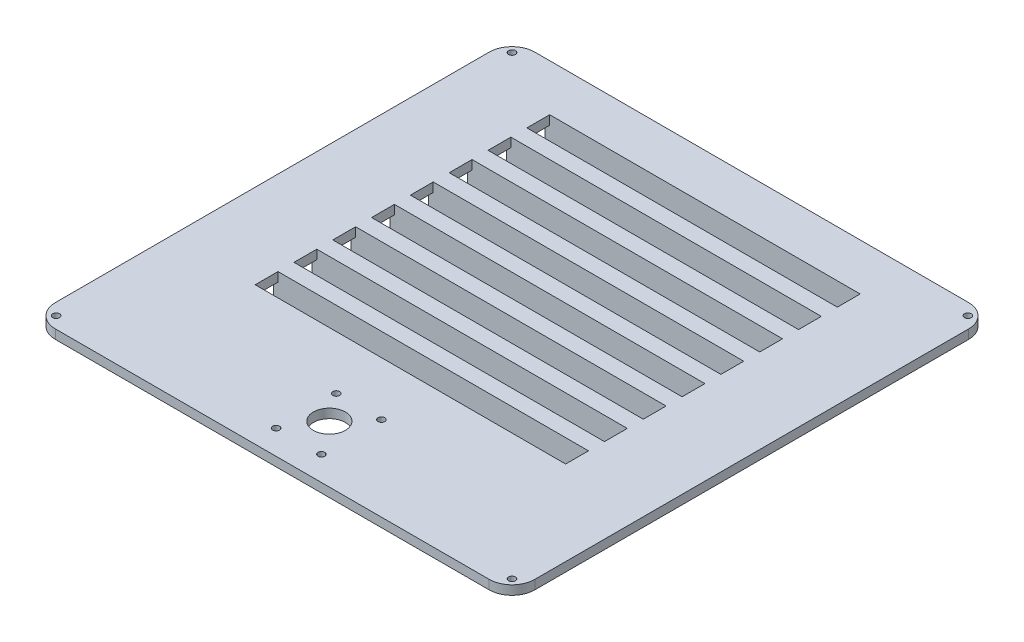
SolidWorks part; units mm, degrees
ref_plane "Front Plane" through (0, 0, 0) normal (0, 0, 1) x (1, 0, 0)
ref_plane "Top Plane" through (0, 0, 0) normal (0, 1, 0) x (1, 0, 0)
ref_plane "Right Plane" through (0, 0, 0) normal (1, 0, 0) x (0, 0, -1)
sketch "Sketch1" plane through (0, 0, 0) normal (0, 1, 0) x (1, 0, 0)
  line L0 (-101, -101) -> (-101, 101)
  line L5 (-105, -105) -> (105, -105)
  line L6 (-105, -105) -> (-105, 105)
  line L7 (-105, 105) -> (105, 105)
  line L8 (105, -105) -> (105, 105)
  line L9 (-101, 101) -> (101, 101)
  line L10 (101, -101) -> (101, 101)
  line L11 (-101, -101) -> (101, -101)
  line L12 (-101, 101) -> (-99.8333, 99.8333) construction
  line L13 (-55, 0) -> (55, 0) construction
  line L14 (-101, -101) -> (-99.8333, -99.8333) construction
  line L15 (0, -55) -> (0, 55) construction
  line L16 (101, -101) -> (99.8333, -99.8333) construction
  line L17 (101, 101) -> (99.8333, 99.8333) construction
  circle A1 centre (-99.8333, 99.8333) radius 1.5
  circle A2 centre (-99.8333, -99.8333) radius 1.5
  circle A3 centre (99.8333, -99.8333) radius 1.5
  circle A4 centre (99.8333, 99.8333) radius 1.5
  point P0 (0, 0)
  point P6 (-105, 0)
  point P7 (0, 105)
  dimension "D3" = 4
  dimension "D4" = 3
  dimension "D1" = 210
  dimension "D2" = 210
  dimension "D5" = 1.65
  dimension "D6" = 45
extrude "MainExtrude" add sketch "Sketch1" along normal blind 4 contours L6 L5 L8 L7
extrude "ScrewHoles" cut sketch "Sketch1<6>" along normal up to surface (4 mm away) contours A1 | A2 | A3 | A4 up to face at (0, 4, 0)
sketch "Sketch1<6>" plane through (0, 0, 0) normal (0, 1, 0) x (1, 0, 0) same geometry as "Sketch1"
fillet "RoundedCorners" radius 10 4 edges at (-105, 2, -105) (-105, 2, 105) (105, 2, -105) (105, 2, 105)
sketch "Sketch3" plane through (0, 0, 0) normal (0, 1, 0) x (1, 0, 0)
  line L145 (-68, 96.5) -> (68, 96.5) construction
  line L146 (-68, 96.5) -> (-68, -56.5) construction
  line L147 (-68, -56.5) -> (68, -56.5) construction
  line L148 (68, 96.5) -> (68, -56.5) construction
  line L149 (-68, 96.5) -> (68, -56.5) construction
  line L151 (68, 96.5) -> (-68, -56.5) construction
  line L152 (-68, 79.5) -> (68, 79.5) construction
  line L154 (-68, 62.5) -> (68, 62.5) construction
  line L155 (-68, 45.5) -> (68, 45.5) construction
  line L157 (-68, 28.5) -> (68, 28.5) construction
  line L158 (-68, 11.5) -> (68, 11.5) construction
  line L159 (-68, -5.5) -> (68, -5.5) construction
  line L160 (-68, -22.5) -> (68, -22.5) construction
  line L161 (-68, -39.5) -> (68, -39.5) construction
  line L162 (-68, 74.5) -> (68, 74.5)
  line L163 (-68, 57.5) -> (68, 57.5)
  line L164 (-68, 40.5) -> (68, 40.5)
  line L165 (-68, 23.5) -> (68, 23.5)
  line L166 (-68, 6.5) -> (68, 6.5)
  line L167 (-68, -10.5) -> (68, -10.5)
  line L168 (-68, -27.5) -> (68, -27.5)
  line L169 (-68, -44.5) -> (68, -44.5)
  line L170 (-68, 84.5) -> (68, 84.5)
  line L171 (-68, 67.5) -> (68, 67.5)
  line L172 (-68, 50.5) -> (68, 50.5)
  line L173 (-68, 33.5) -> (68, 33.5)
  line L174 (-68, 16.5) -> (68, 16.5)
  line L175 (-68, -0.5) -> (68, -0.5)
  line L176 (-68, -17.5) -> (68, -17.5)
  line L177 (-68, -34.5) -> (68, -34.5)
  line L178 (-68, 74.5) -> (-68, 84.5)
  line L179 (68, 74.5) -> (68, 84.5)
  line L180 (-68, 57.5) -> (-68, 67.5)
  line L181 (68, 57.5) -> (68, 67.5)
  line L182 (-68, 40.5) -> (-68, 50.5)
  line L183 (68, 40.5) -> (68, 50.5)
  line L184 (-68, 23.5) -> (-68, 33.5)
  line L185 (68, 23.5) -> (68, 33.5)
  line L186 (-68, 6.5) -> (-68, 16.5)
  line L187 (68, 6.5) -> (68, 16.5)
  line L188 (-68, -10.5) -> (-68, -0.5)
  line L189 (68, -10.5) -> (68, -0.5)
  line L190 (-68, -27.5) -> (-68, -17.5)
  line L191 (68, -27.5) -> (68, -17.5)
  line L192 (-68, -44.5) -> (-68, -34.5)
  line L193 (68, -44.5) -> (68, -34.5)
  line L200 (-9, -68) -> (-9, -94.3) construction
  line L201 (-95, -105) -> (95, -105) construction
  line L207 (-97.2358, 20) -> (95.5763, 20) construction
  line L208 (-9, -68) -> (10.8, -68) construction
  circle A0 centre (0, -80) radius 7
  circle A1 centre (-9, -68) radius 1.5
  circle A2 centre (-9, -94.3) radius 1.5
  circle A3 centre (10.8, -94.3) radius 1.5
  circle A4 centre (10.8, -68) radius 1.5
  point P57 (0, 0)
  point P58 (0, 0)
  point P59 (0, 0)
  point P62 (-1.9194, -80.5562)
  point P70 (0, 20)
  dimension "D18" = 14
  dimension "D19" = 25
  dimension "D21" = 35.5
  dimension "D25" = 3
  dimension "D26" = 3
  dimension "D27" = 19.8
  dimension "D15" = 9
  dimension "D16" = 12
  dimension "D1" = 136
  dimension "D2" = 153
  dimension "D3" = 17
  dimension "D4" = 17
  dimension "D5" = 17
  dimension "D6" = 17
  dimension "D7" = 17
  dimension "D8" = 17
  dimension "D9" = 17
  dimension "D11" = 17
  dimension "D13" = 5
  dimension "D14" = 129
  dimension "D10" = 17
  dimension "D12" = 5
  dimension "D17" = 10.8
  dimension "D20" = 20
  dimension "D22" = 14.3
  dimension "D28" = 26.3
extrude "Trench" cut sketch "Sketch3" along normal blind 10
sketch "Sketch4" plane through (0, 0, 0) normal (0, 1, 0) x (1, 0, 0)
  line L0 (68, -34.5) -> (68, -44.5) construction
  line L1 (68, -44.5) -> (-68, -44.5) construction
  line L2 (-68, -44.5) -> (-68, -34.5) construction
  line L3 (-68, -34.5) -> (68, -34.5) construction
  line L4 (68, -17.5) -> (68, -27.5) construction
  line L5 (68, -27.5) -> (-68, -27.5) construction
  line L6 (-68, -27.5) -> (-68, -17.5) construction
  line L7 (-68, -17.5) -> (68, -17.5) construction
  line L8 (68, -0.5) -> (68, -10.5) construction
  line L9 (68, -10.5) -> (-68, -10.5) construction
  line L10 (-68, -10.5) -> (-68, -0.5) construction
  line L11 (-68, -0.5) -> (68, -0.5) construction
  line L12 (68, 16.5) -> (68, 6.5) construction
  line L13 (68, 6.5) -> (-68, 6.5) construction
  line L14 (-68, 6.5) -> (-68, 16.5) construction
  line L15 (-68, 16.5) -> (68, 16.5) construction
  line L16 (68, 33.5) -> (68, 23.5) construction
  line L17 (68, 23.5) -> (-68, 23.5) construction
  line L18 (-68, 23.5) -> (-68, 33.5) construction
  line L19 (-68, 33.5) -> (68, 33.5) construction
  line L20 (68, 50.5) -> (68, 40.5) construction
  line L21 (68, 40.5) -> (-68, 40.5) construction
  line L22 (-68, 40.5) -> (-68, 50.5) construction
  line L23 (-68, 50.5) -> (68, 50.5) construction
  line L24 (68, 67.5) -> (68, 57.5) construction
  line L25 (68, 57.5) -> (-68, 57.5) construction
  line L26 (-68, 57.5) -> (-68, 67.5) construction
  line L27 (-68, 67.5) -> (68, 67.5) construction
  line L28 (68, 84.5) -> (68, 74.5) construction
  line L29 (68, 74.5) -> (-68, 74.5) construction
  line L30 (-68, 74.5) -> (-68, 84.5) construction
  line L31 (-68, 84.5) -> (68, 84.5) construction
  line L32 (68, -34.5) -> (68, -44.5)
  line L33 (68, -44.5) -> (-68, -44.5)
  line L34 (-68, -44.5) -> (-68, -34.5)
  line L35 (-68, -34.5) -> (68, -34.5)
  line L36 (68, -17.5) -> (68, -27.5)
  line L37 (68, -27.5) -> (-68, -27.5)
  line L38 (-68, -27.5) -> (-68, -17.5)
  line L39 (-68, -17.5) -> (68, -17.5)
  line L40 (68, -0.5) -> (68, -10.5)
  line L41 (68, -10.5) -> (-68, -10.5)
  line L42 (-68, -10.5) -> (-68, -0.5)
  line L43 (-68, -0.5) -> (68, -0.5)
  line L44 (68, 16.5) -> (68, 6.5)
  line L45 (68, 6.5) -> (-68, 6.5)
  line L46 (-68, 6.5) -> (-68, 16.5)
  line L47 (-68, 16.5) -> (68, 16.5)
  line L48 (68, 33.5) -> (68, 23.5)
  line L49 (68, 23.5) -> (-68, 23.5)
  line L50 (-68, 23.5) -> (-68, 33.5)
  line L51 (-68, 33.5) -> (68, 33.5)
  line L52 (68, 50.5) -> (68, 40.5)
  line L53 (68, 40.5) -> (-68, 40.5)
  line L54 (-68, 40.5) -> (-68, 50.5)
  line L55 (-68, 50.5) -> (68, 50.5)
  line L56 (68, 67.5) -> (68, 57.5)
  line L57 (68, 57.5) -> (-68, 57.5)
  line L58 (-68, 57.5) -> (-68, 67.5)
  line L59 (-68, 67.5) -> (68, 67.5)
  line L60 (68, 84.5) -> (68, 74.5)
  line L61 (68, 74.5) -> (-68, 74.5)
  line L62 (-68, 74.5) -> (-68, 84.5)
  line L63 (-68, 84.5) -> (68, 84.5)
  line L64 (70, 86.5) -> (70, 72.5)
  line L65 (70, 72.5) -> (-70, 72.5)
  line L66 (-70, 72.5) -> (-70, 86.5)
  line L67 (-70, 86.5) -> (70, 86.5)
  line L68 (70, 69.5) -> (70, 55.5)
  line L69 (70, 55.5) -> (-70, 55.5)
  line L70 (-70, 55.5) -> (-70, 69.5)
  line L71 (-70, 69.5) -> (70, 69.5)
  line L72 (70, 52.5) -> (70, 38.5)
  line L73 (70, 38.5) -> (-70, 38.5)
  line L74 (-70, 38.5) -> (-70, 52.5)
  line L75 (-70, 52.5) -> (70, 52.5)
  line L76 (70, 35.5) -> (70, 21.5)
  line L77 (70, 21.5) -> (-70, 21.5)
  line L78 (-70, 21.5) -> (-70, 35.5)
  line L79 (-70, 35.5) -> (70, 35.5)
  line L80 (70, 18.5) -> (70, 4.5)
  line L81 (70, 4.5) -> (-70, 4.5)
  line L82 (-70, 4.5) -> (-70, 18.5)
  line L83 (-70, 18.5) -> (70, 18.5)
  line L84 (70, 1.5) -> (70, -12.5)
  line L85 (70, -12.5) -> (-70, -12.5)
  line L86 (-70, -12.5) -> (-70, 1.5)
  line L87 (-70, 1.5) -> (70, 1.5)
  line L88 (70, -15.5) -> (70, -29.5)
  line L89 (70, -29.5) -> (-70, -29.5)
  line L90 (-70, -29.5) -> (-70, -15.5)
  line L91 (-70, -15.5) -> (70, -15.5)
  line L92 (70, -32.5) -> (70, -46.5)
  line L93 (70, -46.5) -> (-70, -46.5)
  line L94 (-70, -46.5) -> (-70, -32.5)
  line L95 (-70, -32.5) -> (70, -32.5)
  dimension "D1" = 2
extrude "Trench Walls" add sketch "Sketch4" against normal blind 4
sketch "Sketch5" plane through (0, -4, 0) normal (0, -1, 0) x (1, 0, 0)
  line L0 (-70, -86.5) -> (70, -86.5) construction
  line L1 (70, -86.5) -> (70, -72.5) construction
  line L2 (70, -72.5) -> (-70, -72.5) construction
  line L3 (-70, -72.5) -> (-70, -86.5) construction
  line L4 (-70, -69.5) -> (70, -69.5) construction
  line L5 (70, -69.5) -> (70, -55.5) construction
  line L6 (70, -55.5) -> (-70, -55.5) construction
  line L7 (-70, -55.5) -> (-70, -69.5) construction
  line L8 (-70, -52.5) -> (70, -52.5) construction
  line L9 (70, -52.5) -> (70, -38.5) construction
  line L10 (70, -38.5) -> (-70, -38.5) construction
  line L11 (-70, -38.5) -> (-70, -52.5) construction
  line L12 (-70, -35.5) -> (70, -35.5) construction
  line L13 (70, -35.5) -> (70, -21.5) construction
  line L14 (70, -21.5) -> (-70, -21.5) construction
  line L15 (-70, -21.5) -> (-70, -35.5) construction
  line L16 (-70, -18.5) -> (70, -18.5) construction
  line L17 (70, -18.5) -> (70, -4.5) construction
  line L18 (70, -4.5) -> (-70, -4.5) construction
  line L19 (-70, -4.5) -> (-70, -18.5) construction
  line L20 (-70, -1.5) -> (70, -1.5) construction
  line L21 (70, -1.5) -> (70, 12.5) construction
  line L22 (70, 12.5) -> (-70, 12.5) construction
  line L23 (-70, 12.5) -> (-70, -1.5) construction
  line L24 (-70, 15.5) -> (70, 15.5) construction
  line L25 (70, 15.5) -> (70, 29.5) construction
  line L26 (70, 29.5) -> (-70, 29.5) construction
  line L27 (-70, 29.5) -> (-70, 15.5) construction
  line L28 (-70, 32.5) -> (70, 32.5) construction
  line L29 (70, 32.5) -> (70, 46.5) construction
  line L30 (70, 46.5) -> (-70, 46.5) construction
  line L31 (-70, 46.5) -> (-70, 32.5) construction
  line L32 (-70, -86.5) -> (70, -86.5)
  line L33 (70, -86.5) -> (70, -72.5)
  line L34 (70, -72.5) -> (-70, -72.5)
  line L35 (-70, -72.5) -> (-70, -86.5)
  line L36 (-70, -69.5) -> (70, -69.5)
  line L37 (70, -69.5) -> (70, -55.5)
  line L38 (70, -55.5) -> (-70, -55.5)
  line L39 (-70, -55.5) -> (-70, -69.5)
  line L40 (-70, -52.5) -> (70, -52.5)
  line L41 (70, -52.5) -> (70, -38.5)
  line L42 (70, -38.5) -> (-70, -38.5)
  line L43 (-70, -38.5) -> (-70, -52.5)
  line L44 (-70, -35.5) -> (70, -35.5)
  line L45 (70, -35.5) -> (70, -21.5)
  line L46 (70, -21.5) -> (-70, -21.5)
  line L47 (-70, -21.5) -> (-70, -35.5)
  line L48 (-70, -18.5) -> (70, -18.5)
  line L49 (70, -18.5) -> (70, -4.5)
  line L50 (70, -4.5) -> (-70, -4.5)
  line L51 (-70, -4.5) -> (-70, -18.5)
  line L52 (-70, -1.5) -> (70, -1.5)
  line L53 (70, -1.5) -> (70, 12.5)
  line L54 (70, 12.5) -> (-70, 12.5)
  line L55 (-70, 12.5) -> (-70, -1.5)
  line L56 (-70, 15.5) -> (70, 15.5)
  line L57 (70, 15.5) -> (70, 29.5)
  line L58 (70, 29.5) -> (-70, 29.5)
  line L59 (-70, 29.5) -> (-70, 15.5)
  line L60 (-70, 32.5) -> (70, 32.5)
  line L61 (70, 32.5) -> (70, 46.5)
  line L62 (70, 46.5) -> (-70, 46.5)
  line L63 (-70, 46.5) -> (-70, 32.5)
extrude "Trench Bottom" add sketch "Sketch5" along normal blind 2
sketch "Sketch7" plane through (70, 0, 0) normal (1, 0, 0) x (0, 0, -1)
  line L1 (-44.5, 0) -> (-34.5, 0)
  line L2 (-44.5, 0) -> (-44.5, -6)
  line L3 (-44.5, -6) -> (-34.5, -6)
  line L4 (-34.5, 0) -> (-34.5, -6)
  line L5 (-46.5, -6) -> (-46.5, 0) construction
  line L6 (-32.5, -6) -> (-46.5, -6) construction
  line L7 (-27.5, 0) -> (-27.5, -6)
  line L8 (-27.5, 0) -> (-17.5, 0)
  line L9 (-17.5, 0) -> (-17.5, -6)
  line L10 (-27.5, -6) -> (-17.5, -6)
  line L11 (-10.5, 0) -> (-10.5, -6)
  line L12 (-10.5, 0) -> (-0.5, 0)
  line L13 (-0.5, 0) -> (-0.5, -6)
  line L14 (-10.5, -6) -> (-0.5, -6)
  line L15 (6.5, 0) -> (6.5, -6)
  line L16 (6.5, 0) -> (16.5, 0)
  line L17 (16.5, 0) -> (16.5, -6)
  line L18 (6.5, -6) -> (16.5, -6)
  line L19 (23.5, 0) -> (23.5, -6)
  line L20 (23.5, 0) -> (33.5, 0)
  line L21 (33.5, 0) -> (33.5, -6)
  line L22 (23.5, -6) -> (33.5, -6)
  line L23 (40.5, 0) -> (40.5, -6)
  line L24 (40.5, 0) -> (50.5, 0)
  line L25 (50.5, 0) -> (50.5, -6)
  line L26 (40.5, -6) -> (50.5, -6)
  line L27 (57.5, 0) -> (57.5, -6)
  line L28 (57.5, 0) -> (67.5, 0)
  line L29 (67.5, 0) -> (67.5, -6)
  line L30 (57.5, -6) -> (67.5, -6)
  line L31 (74.5, 0) -> (74.5, -6)
  line L32 (74.5, 0) -> (84.5, 0)
  line L33 (84.5, 0) -> (84.5, -6)
  line L34 (74.5, -6) -> (84.5, -6)
  line L35 (-29.5, -6) -> (-29.5, 0) construction
  line L36 (-46.5, 0) -> (-32.5, 0) construction
  dimension "D3" = 10
  dimension "D4" = 2
  dimension "D5" = 8
  dimension "D6" = 2
extrude "Wire Opening" cut sketch "Sketch7" against normal through all both and the other way through all
sketch "Sketch9" plane through (0, 0, 0) normal (0, -1, 0) x (1, 0, 0)
  line L0 (-95, 105) -> (95, 105) construction
  line L1 (-70, 46.5) -> (70, 46.5) construction
  line L5 (-105, 95) -> (-105, -95) construction
  circle A0 centre (-94, 92) radius 0.98
  circle A1 centre (-94, 92) radius 2
  circle A2 centre (-19.73, 92) radius 2
  circle A3 centre (-19.73, 92) radius 0.98
  circle A4 centre (-94, 56.16) radius 2
  circle A5 centre (-94, 56.16) radius 0.98
  circle A6 centre (-19.73, 56.16) radius 0.98
  circle A7 centre (-19.73, 56.16) radius 2
  circle A8 centre (-99.8333, 99.8333) radius 1.5 construction
  dimension "D1" = 13
  dimension "D2" = 35.84
  dimension "D5" = 1.96
  dimension "D6" = 4
  dimension "D7" = 1.96
  dimension "D8" = 4
  dimension "D3" = 11
  dimension "D4" = 74.27
  dimension "D9" = 9.7666
  dimension "D10" = 9.66
extrude "PCB Holes" add sketch "Sketch9" along normal blind 4
fillet "PCB Rounds" radius 2 4 edges at (-19.73, 0, 58.16) (-19.73, 0, 94) (-94, 0, 58.16) (-94, 0, 94)
equation "\"1_LED\"= 17mm"
equation "\"2_LED\"= \"1_LED\" * 2"
equation "\"3_LED\"= \"1_LED\" * 3"
equation "\"4_LED\"= \"1_LED\" * 4"
equation "\"5_LED\"= \"1_LED\" * 5"
equation "\"6_LED\"= \"1_LED\" * 6"
equation "\"7_LED\"= \"1_LED\" * 7"
equation "\"8_LED\"= \"1_LED\" * 8"
equation "\"9_LED\"= \"1_LED\" * 9"
equation "\"10_LED\"= \"1_LED\" * 10"
equation "\"11_LED\"= \"1_LED\" * 11"
equation "\"12_LED\"= \"1_LED\" * 12"
